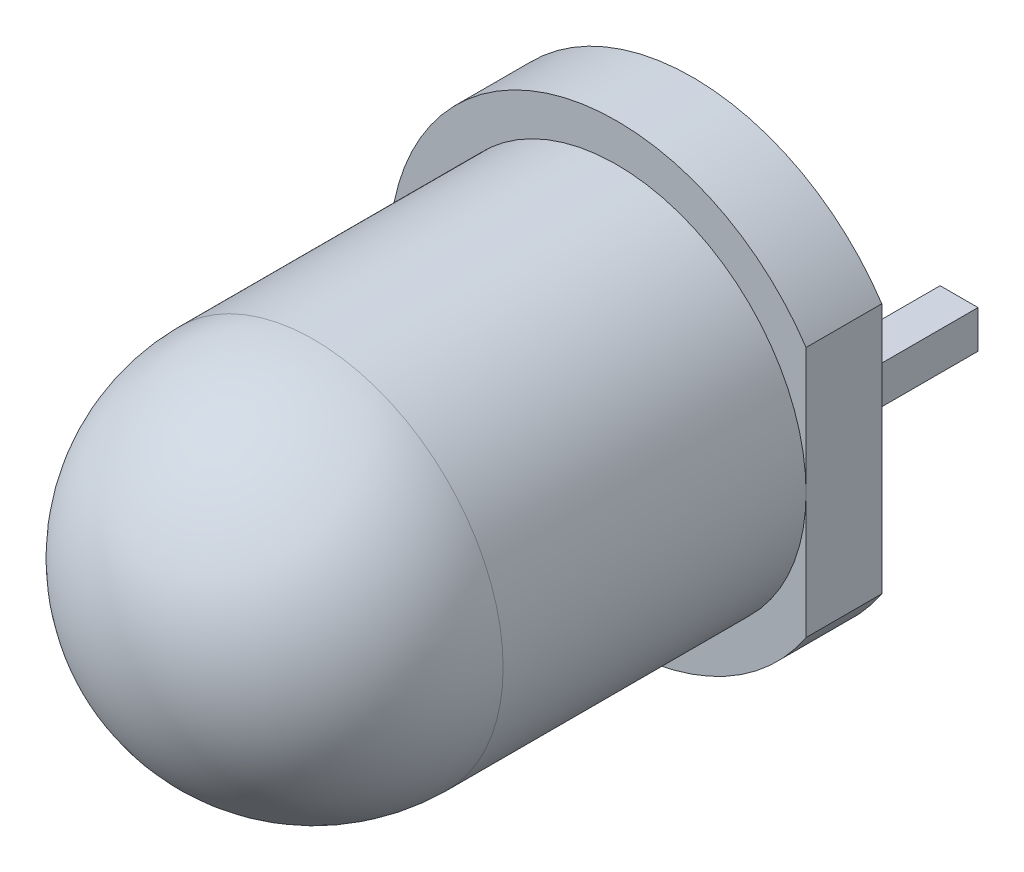
SolidWorks part; units mm, degrees
ref_plane "Front Plane" through (0, 0, 0) normal (0, 0, 1) x (1, 0, 0)
ref_plane "Top Plane" through (0, 0, 0) normal (0, 1, 0) x (1, 0, 0)
ref_plane "Right Plane" through (0, 0, 0) normal (1, 0, 0) x (0, 0, -1)
sketch "Sketch1" plane through (0, 0, 0) normal (0, 0, 1) x (1, 0, 0)
  circle A0 centre (0, 0) radius 3
  dimension "D1" = 6
extrude "Boss-Extrude1" add sketch "Sketch1" along normal blind 1
sketch "Sketch2" plane through (0, 0, 1) normal (0, 0, 1) x (1, 0, 0)
  circle A0 centre (0, 0) radius 2.5
  dimension "D1" = 5
extrude "Boss-Extrude2" add sketch "Sketch2" along normal blind 4
dome "Dome1" faces to dome 1 distance 2.5 reverse direction no elliptical dome no face at (2.5, 0, 5) parameters "D1"=2.5
sketch "Sketch3" plane through (0, 0, 1) normal (0, 0, 1) x (1, 0, 0)
  line L1 (2.5, 1.8503) -> (3, 1.8503)
  line L2 (2.5, 1.8503) -> (2.5, -2.181)
  line L3 (2.5, -2.181) -> (3, -2.181)
  line L4 (3, 1.8503) -> (3, -2.181)
  circle A0 centre (0, 0) radius 3 construction
  circle A1 centre (0, 0) radius 2.5 construction
extrude "Cut-Extrude1" cut sketch "Sketch3" against normal up to next
ref_plane "Plane3" through (0, 0, 0) normal (0, 1, 0) x (1, 0, 0)
sketch "Sketch8" plane through (0, 0, 0) normal (0, 1, 0) x (1, 0, 0)
  line L0 (0, 0) -> (-1.27, 0) construction
  line L1 (2.5, 0) -> (-3, 0) construction
  line L2 (-1.27, 0) -> (-1.27, 2)
  dimension "D1" = 2
  dimension "D2" = 1.27
sheet metal parameters "Sheet-Metal1" thickness 0.5 parameters "D1"=0.1
base flange "Base-Flange1" sketch "Sketch8" end condition mid plane depth 0.5 reverse direction no thickness 0.5 reverse thickness direction no bend radius 0.1
sketch "Sketch9" plane through (0, 0, 0) normal (0, 1, 0) x (1, 0, 0)
  line L0 (1.27, 0) -> (1.27, 2)
  line L1 (-1.27, 2) -> (-0.77, 2) construction
  line L2 (2.5, 0) -> (-3, 0) construction
  dimension "D1" = 1.27
sheet metal parameters "Sheet-Metal2" thickness 0.5 parameters "D1"=0.1
base flange "Base-Flange2" sketch "Sketch9" end condition mid plane depth 0.5 reverse direction no thickness 0.5 reverse thickness direction no bend radius 0.1
sketch "Sketch10" plane through (0, 0, 0) normal (0, 0, -1) x (-1, 0, 0)
  line L0 (0, 0) -> (0, 3) construction
  arc A0 (-2.5, -1.6583) -> (-2.5, 1.6583) centre (0, 0) ccw construction
ref_plane "Plane4" through (0, 0, 0) normal (1, 0, 0) x (0, 0, -1)
ref_axis "Axis1" through (0, 0, 5) along (0, 0, -1)
flat pattern "Flat-Pattern1" [suppressed]
sketch "Bend-Lines1" plane through (0, 0, 0) normal (0, 1, 0) x (1, 0, 0)
sketch3d "Bounding-Box1" [suppressed]
  line L0 (0, 0.5, 0) -> (4.53, 0.5, 0) construction
  line L1 (0, 0, 0) -> (4.53, 0, 0) construction
  line L2 (0, 0.5, 0) -> (0, 0, 0) construction
  line L3 (4.53, 0.5, 0) -> (4.53, 0, 0) construction
flat pattern "Flat-Pattern2" [suppressed]
sketch "Bend-Lines2" plane through (0, 0, 0) normal (0, 1, 0) x (1, 0, 0)
sketch "Bounding-Box2" [suppressed] plane through (0, 0, 0) normal (0, 1, 0) x (1, 0, 0)
